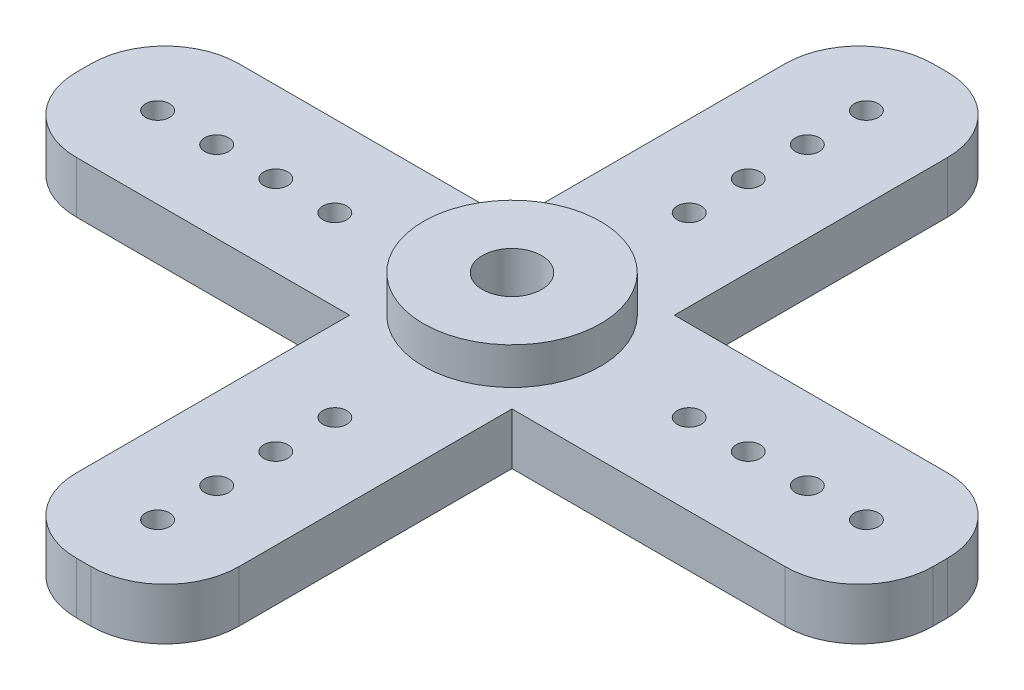
SolidWorks part; units mm, degrees
ref_plane "Front Plane" through (0, 0, 0) normal (0, 0, 1) x (1, 0, 0)
ref_plane "Top Plane" through (0, 0, 0) normal (0, 1, 0) x (1, 0, 0)
ref_plane "Right Plane" through (0, 0, 0) normal (1, 0, 0) x (0, 0, -1)
sketch "Sketch1" plane through (0, 0, 0) normal (0, 1, 0) x (1, 0, 0)
  line L0 (0, -1000) -> (0, 49000) construction
  line L1 (-2.75, 14.5) -> (2.75, 14.5)
  line L2 (-2.75, 14.5) -> (-2.75, 0)
  line L3 (-2.75, 0) -> (2.75, 0)
  line L4 (2.75, 14.5) -> (2.75, 0)
  circle A0 centre (0, 12) radius 0.4064
  circle A1 centre (0, 10) radius 0.4064
  circle A2 centre (0, 8) radius 0.4064
  circle A3 centre (0, 6) radius 0.4064
  point P4 (0, 0)
  dimension "D3" = 0.8128
  dimension "D1" = 5.5
  dimension "D2" = 14.5
  dimension "D4" = 12
  dimension "D5" = 4
extrude "Boss-Extrude1" add sketch "Sketch1" along normal blind 1.75
fillet "Fillet1" radius 2.5 2 edges at (-2.75, 0.875, -14.5) (2.75, 0.875, -14.5)
ref_axis "Axis1" through (0, 0, 0) along (0, 1, 0)
pattern_circular "CirPattern1" count 4 over 360 about axis through (0, 0, 0) along (0, 1, 0) of "Boss-Extrude1", "Fillet1"
sketch "Sketch2" plane through (0, 1.75, 0) normal (0, 1, 0) x (1, 0, 0)
  circle A0 centre (0, 0) radius 1
extrude "Cut-Extrude1" cut sketch "Sketch2" against normal up to next
sketch "Sketch3" plane through (0, 1.75, 0) normal (0, 1, 0) x (1, 0, 0)
  circle A0 centre (0, 0) radius 1
  circle A1 centre (0, 0) radius 3
  dimension "D1" = 6
extrude "Boss-Extrude2" add sketch "Sketch3" along normal blind 1.25
